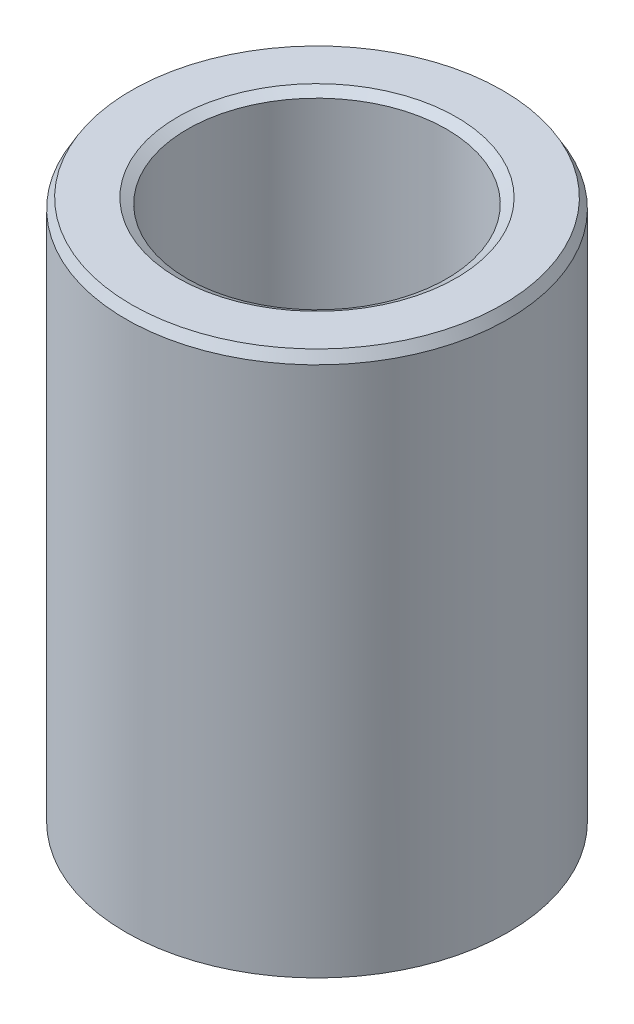
SolidWorks part; units mm, degrees
ref_plane "Front Plane" through (0, 0, 0) normal (0, 0, 1) x (1, 0, 0)
ref_plane "Top Plane" through (0, 0, 0) normal (0, 1, 0) x (1, 0, 0)
ref_plane "Right Plane" through (0, 0, 0) normal (1, 0, 0) x (0, 0, -1)
sketch "Sketch1" plane through (0, 0, 0) normal (0, 1, 0) x (1, 0, 0)
  circle A0 centre (0, 0) radius 35
  dimension "SLEEVE_OD" = 70
extrude "Boss-Extrude1" add sketch "Sketch1" along normal blind 100.0209
sketch "Sketch2" plane through (0, 0, 0) normal (0, 1, 0) x (1, 0, 0)
  circle A0 centre (0, 0) radius 23.7299
  dimension "BORE_D" = 47.4597
extrude "Cut-Extrude1" cut sketch "Sketch2" along normal through all
chamfer "Chamfer1" distance 1.7894 angle 30 4 edges at (0, 100.0209, 23.7299) (0, 0, 23.7299) (0, 0, 35) (0, 100.0209, 35) first distance on face at (0, 100.0209, 23.7299) first distance on face at (0, 0, 23.7299) first distance on face at (0, 100.0209, 35)
